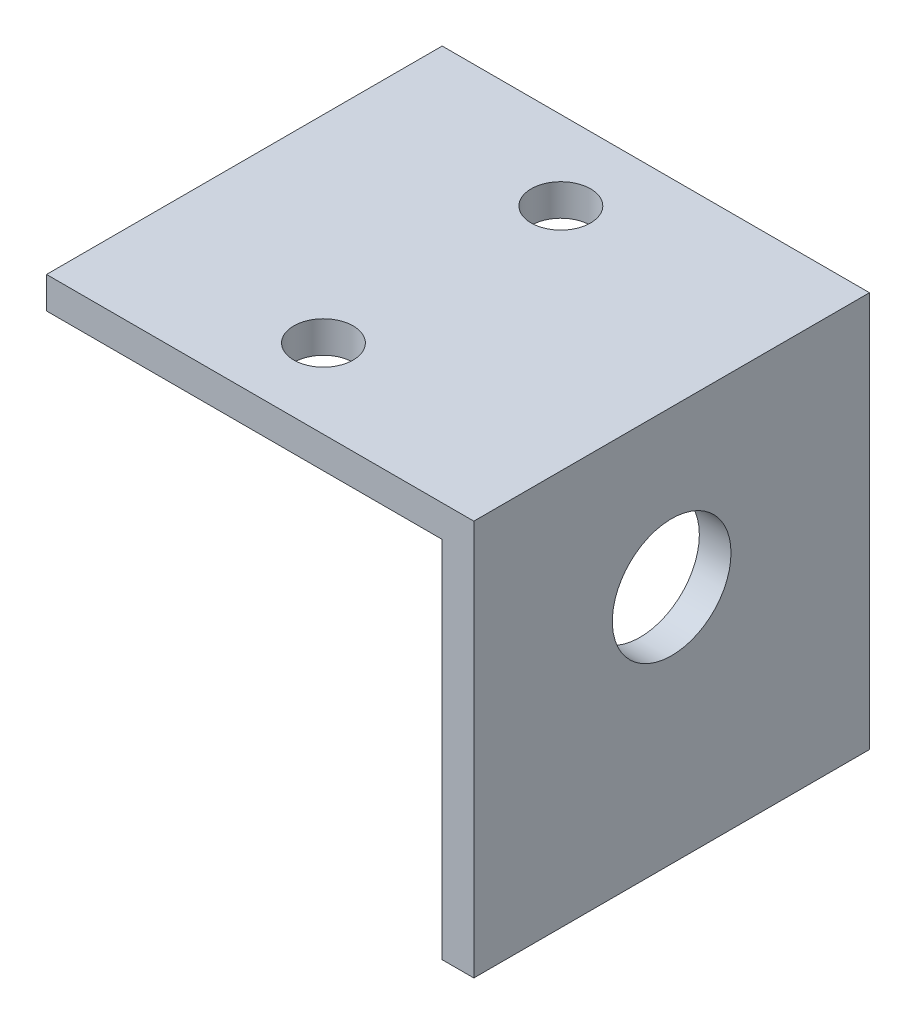
SolidWorks part; units mm, degrees
ref_plane "Front Plane" through (0, 0, 0) normal (0, 0, 1) x (1, 0, 0)
ref_plane "Top Plane" through (0, 0, 0) normal (0, 1, 0) x (1, 0, 0)
ref_plane "Right Plane" through (0, 0, 0) normal (1, 0, 0) x (0, 0, -1)
sketch "Sketch2" plane through (0, 0, 0) normal (0, 1, 0) x (1, 0, 0)
  line L1 (-10, -10) -> (10, -10)
  line L2 (-10, -10) -> (-10, 10)
  line L3 (-10, 10) -> (10, 10)
  line L4 (10, -10) -> (10, 10)
  line L5 (-10, -10) -> (10, 10) construction
  line L6 (-10, 10) -> (10, -10) construction
  line L7 (10, 10) -> (11.6, 10)
  line L8 (10, 10) -> (10, -10)
  line L9 (10, -10) -> (11.6, -10)
  line L10 (11.6, 10) -> (11.6, -10)
  point P0 (0, 0)
  dimension "D1" = 20
  dimension "D2" = 20
  dimension "D3" = 1.6
extrude "Boss-Extrude1" add sketch "Sketch2" against normal blind 1.6 contours L1 L4 L3 L2 region at (0, 0, 0)
extrude "Boss-Extrude2" add sketch "Sketch2<4>" against normal blind 20 contours L10 L7 L4 L9 region at (10.8, 0, 0)
sketch "Sketch2<4>" plane through (0, 0, 0) normal (0, 1, 0) x (1, 0, 0) same geometry as "Sketch2"
sketch "Sketch3" plane through (11.6, 0, 0) normal (1, 0, 0) x (0, 0, -1)
  line L2 (10, -20) -> (10, 0) construction
  line L6 (10, 0) -> (-10, 0) construction
  circle A0 centre (0, -7.8887) radius 3
  point P10 (1.7837, 14.9064)
  point P11 (0, 0)
  dimension "D1" = 6
  dimension "D2" = 10
  dimension "D3" = 7.8887
extrude "Cut-Extrude1" cut sketch "Sketch3" against normal blind 3
sketch "Sketch4" plane through (0, 0, 0) normal (0, 1, 0) x (1, 0, 0)
  line L0 (-10, -10) -> (-10, 10) construction
  line L1 (-10, -10) -> (11.6, -10) construction
  line L2 (-10, 10) -> (11.6, 10) construction
  circle A0 centre (0, 6) radius 1.5
  circle A1 centre (0, -6) radius 1.5
  dimension "D1" = 10
  dimension "D2" = 3
  dimension "D6" = 3
  dimension "D3" = 4
  dimension "D4" = 10
  dimension "D5" = 4
extrude "Cut-Extrude2" cut sketch "Sketch4" against normal blind 2
